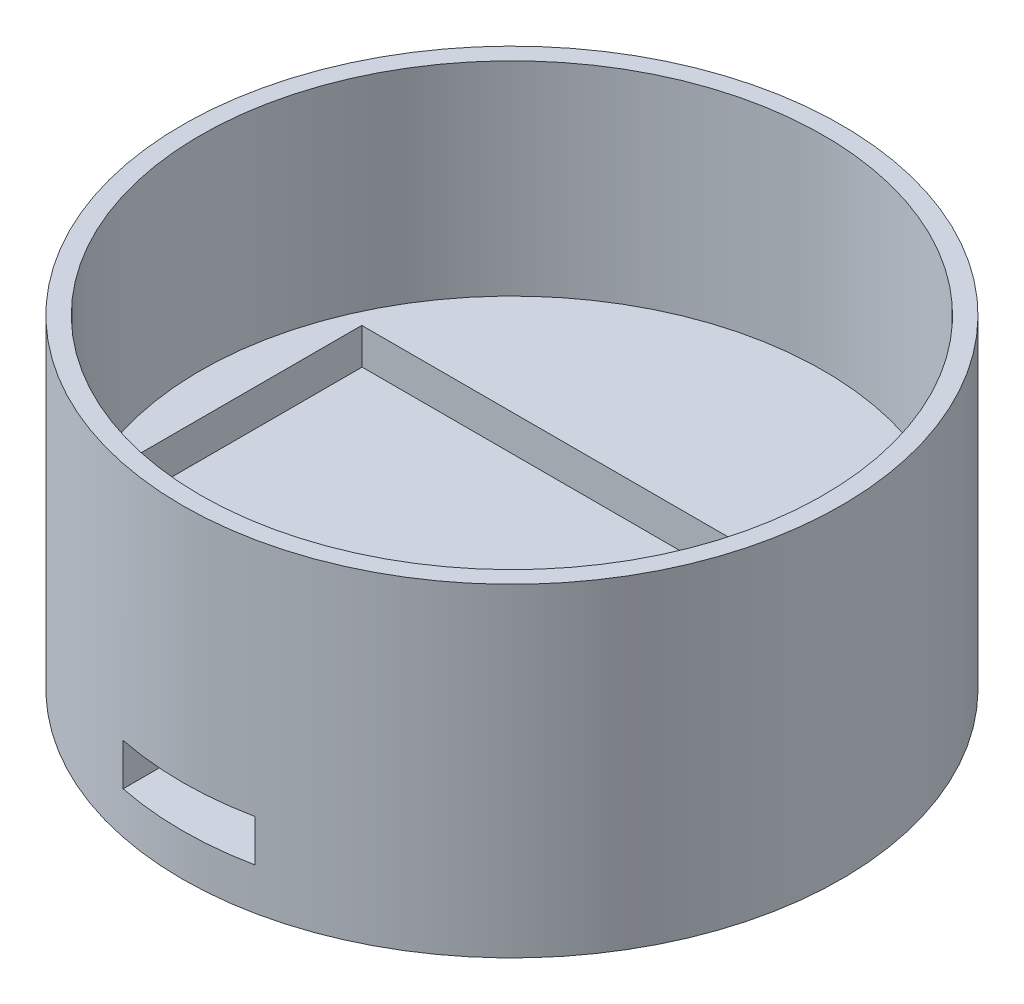
SolidWorks part; units mm, degrees
ref_plane "Front Plane" through (0, 0, 0) normal (0, 0, 1) x (1, 0, 0)
ref_plane "Top Plane" through (0, 0, 0) normal (0, 1, 0) x (1, 0, 0)
ref_plane "Right Plane" through (0, 0, 0) normal (1, 0, 0) x (0, 0, -1)
sketch "Sketch1" plane through (0, 0, 0) normal (0, 1, 0) x (1, 0, 0)
  line L0 (-4.0671, 7.5) -> (3.7836, 7.5) construction
  line L2 (-22.5, -10) -> (-22.5, 10)
  line L4 (22.5, -10) -> (22.5, 10)
  line L5 (-22.5, -10) -> (22.5, 10) construction
  line L6 (-22.5, 10) -> (22.5, -10) construction
  line L7 (-22.5303, -10) -> (22.4697, -10)
  line L8 (-22.5303, -10) -> (-22.5303, 10)
  line L9 (-22.5303, 10) -> (22.4697, 10)
  line L10 (22.4697, -10) -> (22.4697, 10)
  line L11 (-4.0671, 9.5) -> (3.7836, 9.5)
  line L12 (-4.0671, 5.5) -> (3.7836, 5.5)
  line L13 (-4.0671, 7.5) -> (3.7836, 7.5) construction
  line L14 (-4.0671, 9) -> (3.7836, 9)
  line L15 (-4.0671, 6) -> (3.7836, 6)
  circle A0 centre (0, 0) radius 27.5
  circle A1 centre (0, 0) radius 26
  circle A2 centre (12.9697, 0) radius 8
  circle A3 centre (-13.0303, 0) radius 8
  circle A4 centre (-20.5303, 8.2533) radius 1
  circle A5 centre (20.4697, -8.2467) radius 1
  arc A6 (-4.0671, 9.5) -> (-4.0671, 5.5) centre (-4.0671, 7.5) ccw
  arc A7 (3.7836, 5.5) -> (3.7836, 9.5) centre (3.7836, 7.5) ccw
  arc A8 (-4.0671, 9) -> (-4.0671, 6) centre (-4.0671, 7.5) ccw
  arc A9 (3.7836, 6) -> (3.7836, 9) centre (3.7836, 7.5) ccw
  circle A10 centre (-13.0303, 0) radius 6.5
  circle A11 centre (12.9697, 0) radius 6.5
  circle A12 centre (20.4697, 8.8958) radius 1
  circle A13 centre (-20.5303, -7.6042) radius 1
  point P21 (-0.1418, 7.5)
  point P28 (-0.1418, 7.5)
  dimension "D3" = 55
  dimension "D4" = 1.5
  dimension "D8" = 16
  dimension "D9" = 16
  dimension "D11" = 2
  dimension "D12" = 2
  dimension "D16" = 2
  dimension "D17" = 1.5
  dimension "D18" = 13
  dimension "D19" = 13
  dimension "D20" = 2
  dimension "D21" = 2
  dimension "D23" = 10
  dimension "D1" = 45
  dimension "D2" = 20
  dimension "D5" = 45
  dimension "D6" = 20
  dimension "D7" = 26
  dimension "D10" = 9.5
  dimension "D13" = 41
  dimension "D14" = 16.5
  dimension "D15" = 2
  dimension "D22" = 2.5
extrude "Boss-Extrude1" add sketch "Sketch1" along normal blind 20 contours A0 A1 region at (-26.7222, 0, 0)
extrude "Boss-Extrude2" add sketch "Sketch1<3>" along normal blind 3 contours A1 L10 L7 L8 L9 region at (-25.2646, 0, 0)
sketch "Sketch1<3>" plane through (0, 0, 0) normal (0, 1, 0) x (1, 0, 0) same geometry as "Sketch1"
extrude "Boss-Extrude3" add sketch "Sketch1<4>" along direction (0, 1, 0) on the side against the normal blind 7 contours A0 A1 | A1 L10 L7 L8 L9 | A4 | A5 | A12 | L7 L10 L9 L8 A13 A12 A7 L12 A6 L11 A5 A4 A3 A2 | A10 | A3 A10 | L15 A9 L14 A8 | L12 A7 L11 A6 A9 L15 A8 L14 | A11 | A2 A11 | A13 region at (0.0117, 0, 0.7575) region at (-0.1418, 0, -9.3749) region at (-0.1418, 0, -7.5) region at (-26.7222, 0, 0) region at (-25.2646, 0, 0) region at (5.196, 0, 0) region at (-20.804, 0, 0) region at (-20.5303, 0, -8.2533) region at (20.4697, 0, 8.2467) region at (-13.0303, 0, 0) region at (12.9697, 0, 0) region at (20.4697, 0, -8.8958)
sketch "Sketch1<4>" plane through (0, 0, 0) normal (0, 1, 0) x (1, 0, 0) same geometry as "Sketch1"
sketch "Sketch4" plane through (0, 0, 10) normal (0, 0, -1) x (-1, 0, 0)
  line L0 (-5.5, 0) -> (5.5, 0)
  line L1 (-5.5, -3.5) -> (5.5, -3.5)
  line L2 (-5.5, -3.5) -> (-5.5, 0)
  line L4 (5.5, -3.5) -> (5.5, 0)
  point P0 (0, 0)
extrude "Cut-Extrude3" cut sketch "Sketch4" against normal mid plane 5
extrude "Cut-Extrude4" cut sketch "Sketch4<2>" against normal through all
sketch "Sketch4<2>" plane through (0, 0, 10) normal (0, 0, -1) x (-1, 0, 0) same geometry as "Sketch4"
